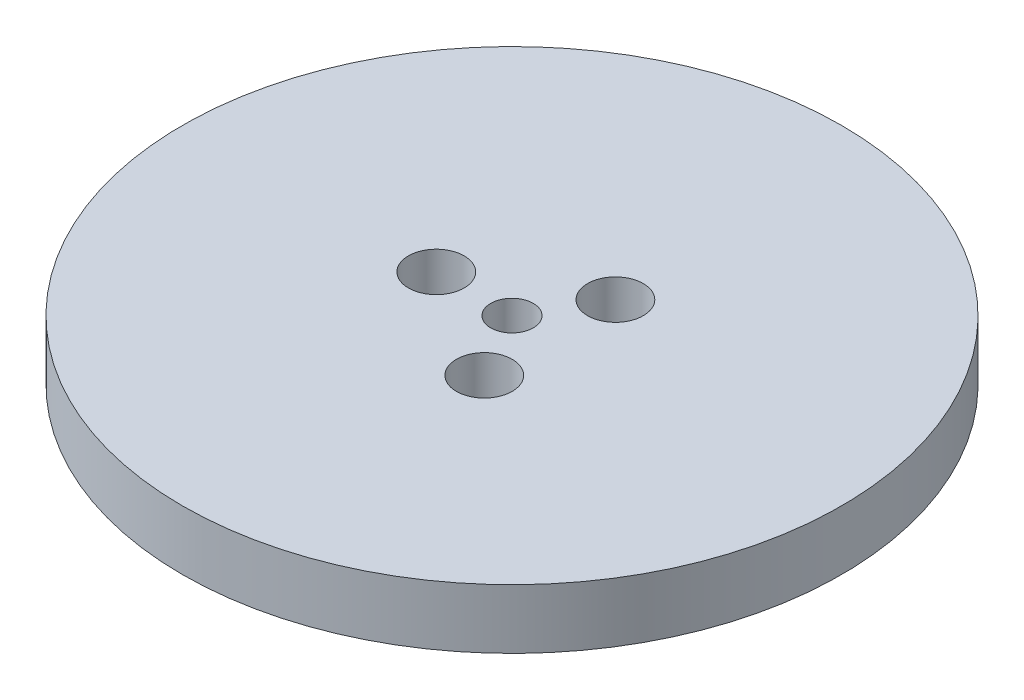
SolidWorks part; units mm, degrees
ref_plane "Front Plane" through (0, 0, 0) normal (0, 0, 1) x (1, 0, 0)
ref_plane "Top Plane" through (0, 0, 0) normal (0, 1, 0) x (1, 0, 0)
ref_plane "Right Plane" through (0, 0, 0) normal (1, 0, 0) x (0, 0, -1)
sketch "Sketch1" plane through (0, 0, 0) normal (0, 1, 0) x (1, 0, 0)
  circle A0 centre (0, 0) radius 77.5
  dimension "FLANGE_OD" = 155
extrude "Boss-Extrude1" add sketch "Sketch1" along normal blind 14
sketch "Sketch2" plane through (0, 0, 0) normal (0, 1, 0) x (1, 0, 0)
  circle A0 centre (0, 0) radius 5
  dimension "BORE_D" = 10
extrude "Cut-Extrude1" cut sketch "Sketch2" along normal through all
sketch "Sketch3" plane through (0, 14, 0) normal (0, 1, 0) x (1, 0, 0)
  circle A0 centre (0, 0) radius 17.8039 construction
  circle A1 centre (-17.8039, 0) radius 6.5543
  dimension "BOLT_D" = 13.1085
  dimension "BOLT_PCD" = 35.6079
extrude "Cut-Extrude2" cut sketch "Sketch3" against normal blind 13.4743
pattern_circular "CirPattern1" count 3 over 360 about axis through (0, 0, 0) along (0, 1, 0) of "Cut-Extrude2"
